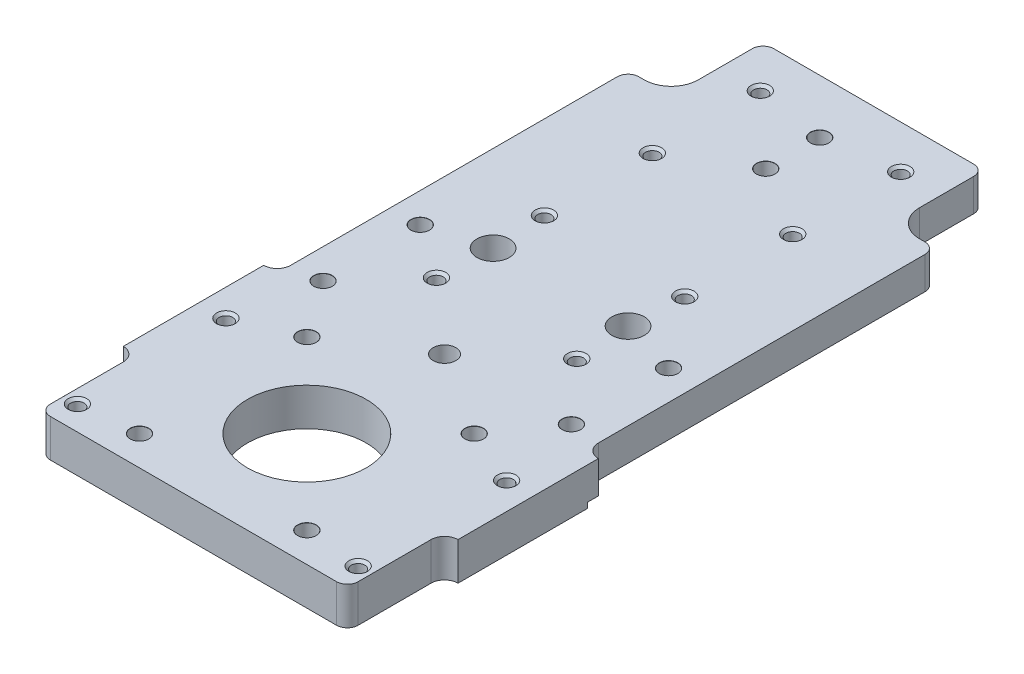
SolidWorks part; units mm, degrees
ref_plane "Top" through (0, 0, 0) normal (0, 0, 1) x (1, 0, 0)
ref_plane "Front" through (0, 0, 0) normal (0, 1, 0) x (1, 0, 0)
ref_plane "Right" through (0, 0, 0) normal (1, 0, 0) x (0, 0, -1)
sketch "Plate Main Sketch" plane through (-158.0855, 0, 24.6791) normal (0, 1, 0) x (-1, 0, 0)
  line L1 (-178.5855, -24.6791) -> (-137.5855, -24.6791)
  line L2 (-127.0855, 57.3209) -> (-127.0855, 83.3209)
  line L3 (-129.5855, 101.3209) -> (-186.5855, 101.3209)
  line L4 (-129.5855, 101.3209) -> (-129.5855, 85.8209)
  line L5 (-158.0855, 101.3209) -> (-158.0855, -24.6791) construction
  line L6 (-178.5855, -12.6791) -> (-178.5855, -24.6791)
  line L7 (-129.5855, 54.8209) -> (-129.5855, -7.6791)
  line L8 (-129.5855, -7.6791) -> (-132.5855, -7.6791)
  line L9 (-137.5855, -12.6791) -> (-137.5855, -24.6791)
  line L10 (-186.5855, -7.6791) -> (-183.5855, -7.6791)
  line L11 (-186.5855, 54.8209) -> (-186.5855, -7.6791)
  line L12 (-189.0855, 57.3209) -> (-189.0855, 83.3209)
  line L13 (-186.5855, 101.3209) -> (-186.5855, 85.8209)
  arc A0 (-129.5855, 85.8209) -> (-127.0855, 83.3209) centre (-127.0855, 85.8209) ccw
  arc A1 (-129.5855, 54.8209) -> (-127.0855, 57.3209) centre (-127.0855, 54.8209) cw
  arc A2 (-132.5855, -7.6791) -> (-137.5855, -12.6791) centre (-132.5855, -12.6791) ccw
  arc A3 (-183.5855, -7.6791) -> (-178.5855, -12.6791) centre (-183.5855, -12.6791) cw
  arc A4 (-186.5855, 54.8209) -> (-189.0855, 57.3209) centre (-189.0855, 54.8209) ccw
  arc A5 (-186.5855, 85.8209) -> (-189.0855, 83.3209) centre (-189.0855, 85.8209) cw
  circle A18 centre (-158.0855, 80.3209) radius 11
  circle A20 centre (-145.5855, 33.3209) radius 3
  circle A21 centre (-170.5855, 33.3209) radius 3
  dimension "D2" = 5
  dimension "D8" = 22
  dimension "D9" = 6
  dimension "D1" = 2.5
  dimension "D3" = 62
  dimension "D4" = 126
  dimension "D5" = 18
  dimension "D6" = 44
  dimension "D15" = 21
  dimension "D17" = 8
  dimension "D7" = 109
  dimension "D10" = 58
  dimension "D11" = 16
extrude "Extrude Plate Main" add sketch "Plate Main Sketch" along normal blind 7
fillet "Corner Fillets" radius 2 6 edges at (-28.5, 3.5, 126) (-28.5, 3.5, 17) (-20.5, 3.5, 0) (20.5, 3.5, 0) (28.5, 3.5, 17) (28.5, 3.5, 126)
sketch "Reccess Sketch" plane through (0, 0, 0) normal (0, 1, 0) x (1, 0, 0)
  line L0 (-8.25, 0) -> (-8.25, -81)
  line L1 (-11.25, -84) -> (-31, -84)
  line L2 (-31, -84) -> (-31, 0)
  line L3 (-31, 0) -> (-8.25, 0)
  line L4 (0, 0) -> (0, -84) construction
  line L5 (31, 0) -> (8.25, 0)
  line L6 (8.25, 0) -> (8.25, -81)
  line L7 (31, -84) -> (31, 0)
  line L8 (11.25, -84) -> (31, -84)
  arc A0 (-8.25, -81) -> (-11.25, -84) centre (-11.25, -81) cw
  arc A1 (8.25, -81) -> (11.25, -84) centre (11.25, -81) ccw
  point P7 (-8.25, -84)
  dimension "D4" = 3
  dimension "D1" = 84
  dimension "D2" = 31
  dimension "D3" = 22.75
hole_wizard "M3x0.5 Tapped Holes" positions "Sketch12" profile "Sketch13" tap size "M3x0.5" standard "ANSI Metric" end condition through all
sketch "Sketch12" plane through (0, 0, 0) normal (0, -1, 0) x (-1, 0, 0)
  line L0 (-13, -8) -> (-13, -68) construction
  line L2 (13, -68) -> (13, -8) construction
  line L4 (26, -121.5) -> (-26, -121.5) construction
  line L5 (-26, -121.5) -> (-26, -94) construction
  line L6 (-26, -94) -> (26, -94) construction
  line L7 (26, -94) -> (26, -121.5) construction
  line L11 (31, -126) -> (-31, -126) construction
  line L12 (31, -126) -> (31, 0) construction
  line L13 (31, 0) -> (-31, 0) construction
  line L14 (-31, -126) -> (-31, 0) construction
  line L15 (0, 0) -> (0, -126) construction
  line L16 (31, -63) -> (-31, -63) construction
  point P0 (-26, -121.5)
  point P2 (-26, -94)
  point P4 (26, -94)
  point P8 (13, -68)
  point P10 (13, -48)
  point P12 (13, -28)
  point P14 (13, -8)
  point P16 (-13, -8)
  point P18 (-13, -28)
  point P20 (-13, -48)
  point P22 (-13, -68)
  point P477 (26, -121.5)
  dimension "D1" = 126
  dimension "D2" = 62
  dimension "D3" = 118
  dimension "D4" = 98
  dimension "D5" = 78
  dimension "D6" = 58
  dimension "D7" = 18
  dimension "D8" = 18
  dimension "D9" = 5
  dimension "D10" = 5
  dimension "D11" = 4.5
  dimension "D12" = 32
sketch "Sketch13" plane through (26, 0, 121.5) normal (1, 0, 0) x (0, 0, -1)
  line L0 (0, 0) -> (0, 7)
  line L1 (0, 7) -> (1.725, 7)
  line L2 (1.25, 6.525) -> (1.25, 0)
  line L5 (1.25, 0) -> (0, 0)
  line L7 (1.725, 7) -> (1.25, 6.525)
  line L8 (-1.725, 7) -> (-1.25, 6.525) construction
  line L11 (0, -6.35) -> (0, 107.95) construction
  dimension "Thru Tap Drill Dia." = 2.5
  dimension "Thru Tap Drill Depth" = 7
  dimension "Far C'Sink Dia." = 3.45
  dimension "Far C'Sink Angle" = 90
cosmetic thread "Hole Thread54" parameters "D2"=3
cosmetic thread "Hole Thread55" parameters "D2"=3
cosmetic thread "Hole Thread56" parameters "D2"=3
cosmetic thread "Hole Thread57" parameters "D2"=3
cosmetic thread "Hole Thread58" parameters "D2"=3
cosmetic thread "Hole Thread59" parameters "D2"=3
cosmetic thread "Hole Thread60" parameters "D2"=3
cosmetic thread "Hole Thread61" parameters "D2"=3
cosmetic thread "Hole Thread62" parameters "D2"=3
cosmetic thread "Hole Thread63" parameters "D2"=3
cosmetic thread "Hole Thread64" parameters "D2"=3
cosmetic thread "Hole Thread65" parameters "D2"=3
hole_wizard "M3 Counter Bores" positions "Sketch4" profile "Sketch5" counterbore size "M3" standard "ANSI Metric" end condition through all
sketch "Sketch4" plane through (0, 0, 0) normal (0, -1, 0) x (-1, 0, 0)
  line L0 (31, -126) -> (-31, -126) construction
  line L1 (-31, -126) -> (-31, 0) construction
  line L2 (-31, 0) -> (31, 0) construction
  line L3 (31, 0) -> (31, -126) construction
  line L5 (15.5, -120.5) -> (-15.5, -120.5) construction
  line L6 (-15.5, -120.5) -> (-15.5, -89.5) construction
  line L7 (-15.5, -89.5) -> (15.5, -89.5) construction
  line L8 (15.5, -89.5) -> (15.5, -120.5) construction
  line L10 (0, -126) -> (0, 0) construction
  point P0 (15.5, -120.5)
  point P3 (-15.5, -120.5)
  point P6 (-15.5, -89.5)
  point P9 (15.5, -89.5)
  point P12 (23, -79)
  point P15 (-23, -79)
  point P18 (-23, -61)
  point P21 (23, -61)
  point P24 (0, -20)
  point P27 (0, -10)
  point P42 (0, 0)
  point P65 (0, -120.5)
  dimension "D1" = 126
  dimension "D2" = 62
  dimension "D3" = 31
  dimension "D4" = 31
  dimension "D5" = 5.5
  dimension "D6" = 47
  dimension "D7" = 65
  dimension "D8" = 106
  dimension "D9" = 116
  dimension "D10" = 8
  dimension "D11" = 8
sketch "Sketch5" plane through (-15.5, 0, 120.5) normal (1, 0, 0) x (0, 0, -1)
  line L0 (0, 0) -> (0, 7)
  line L1 (1.7, 6.975) -> (1.725, 7)
  line L2 (1.7, 6.975) -> (1.7, 4.5)
  line L3 (1.7, 4.5) -> (3, 4.5)
  line L4 (3, 4.5) -> (3, 0)
  line L5 (3, 0) -> (0, 0)
  line L11 (0, -6.35) -> (0, 107.95) construction
  line L12 (1.725, 7) -> (0, 7)
  line L13 (-1.7, 6.975) -> (-1.725, 7) construction
  dimension "Thru Hole Dia." = 3.4
  dimension "Thru Hole Depth" = 7
  dimension "C'Bore Dia." = 6
  dimension "C'Bore Depth" = 4.5
  dimension "Far C'Sink Dia." = 3.45
  dimension "Far C'Sink Angle" = 90
hole_wizard "M5x0.8 Tapped Hole1" positions "Sketch14" profile "Sketch15" tap size "M5x0.8" standard "ANSI Metric" end condition through all
sketch "Sketch14" plane through (0, 0, 0) normal (0, -1, 0) x (-1, 0, 0)
  point P0 (0, -79.5)
  dimension "D1" = 79.5
sketch "Sketch15" plane through (0, 0, 79.5) normal (1, 0, 0) x (0, 0, -1)
  line L0 (0, 0) -> (0, 7)
  line L1 (0, 7) -> (2.1, 7)
  line L2 (2.1, 7) -> (2.1, 0)
  line L5 (2.1, 0) -> (0, 0)
  line L11 (0, -6.35) -> (0, 107.95) construction
  dimension "Thru Tap Drill Dia." = 4.2
  dimension "Thru Tap Drill Depth" = 7
cosmetic thread "Hole Thread66" parameters "D2"=5
extrude "Cut Recess" cut sketch "Reccess Sketch" along normal blind 1
equation "\"M2 Close Fit Hole\"= 2.2"
equation "\"M2.5 Close Fit Hole\"= 2.7"
equation "\"M3 Close Fit Hole\"= 3.2"
equation "\"M4 Close Fit Hole\"= 4.3"
equation "\"M5 Close Fit Hole\"= 5.3"
equation "\"M6 Close Fit Hole\"= 6.3"
equation "\"M7 Close Fit Hole\"= 7.4"
equation "\"M8 Close Fit Hole\"= 8.4"
equation "\"M2 Tap Hole 75%\"= 1.6"
equation "\"M3 Tap Hole 75%\"= 2.5"
equation "\"M4 Tap Hole 75%\"= 3.3"
equation "\"M5 Tap Hole 75%\"= 4.2"
equation "\"M6 Tap Hole 75%\"= 5"
equation "\"M7 Tap Hole 75%\"= 6"
equation "\"M8 Tap Hole 75%\"= 6.8"
equation "\"Bracket Width\"= 62mm"
equation "\"D3@Plate Main Sketch\"=\"Bracket Width\""
equation "\"Bracket Height\"= 126mm"
equation "\"D4@Plate Main Sketch\"=\"Bracket Height\""
equation "\"D1@Sketch4\"=\"Bracket Height\""
equation "\"D2@Sketch4\"=\"Bracket Width\""
equation "\"D1@Sketch12\"=\"Bracket Height\""
equation "\"D2@Sketch12\"=\"Bracket Width\""
equation "\"D2@Reccess Sketch\" = 0.5 * \"Bracket Width\""
